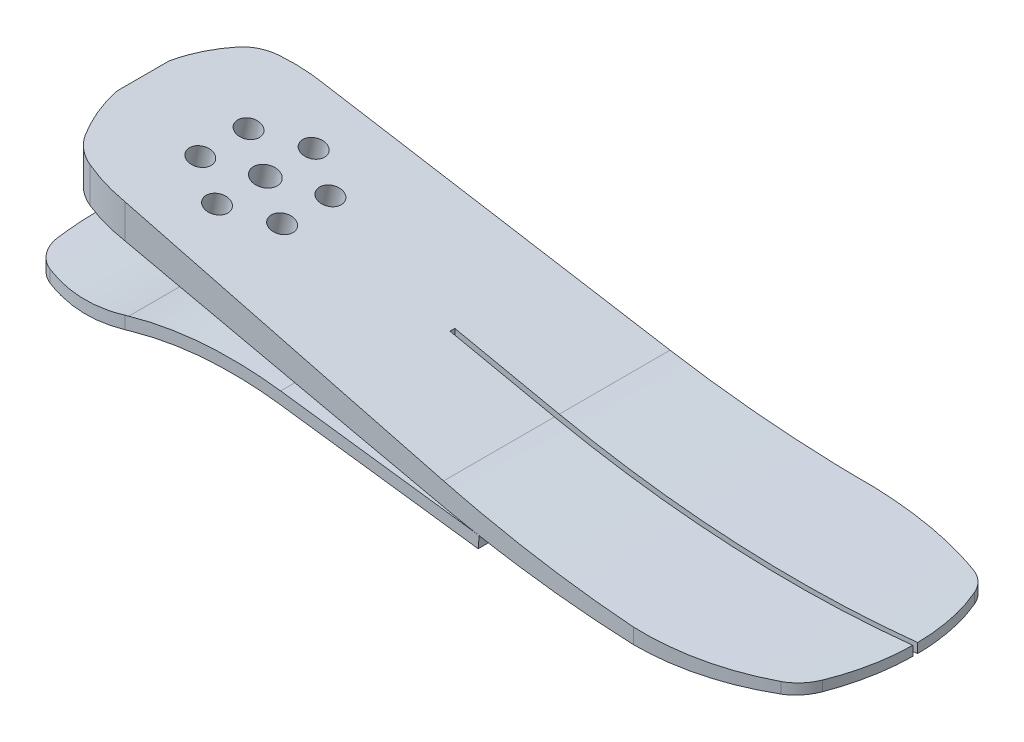
SolidWorks part; units mm, degrees
material "Thornel Mat VMA"
ref_plane "前视基准面" through (0, 0, 0) normal (0, 0, 1) x (1, 0, 0)
ref_plane "上视基准面" through (0, 0, 0) normal (0, 1, 0) x (1, 0, 0)
ref_plane "右视基准面" through (0, 0, 0) normal (1, 0, 0) x (0, 0, -1)
sketch "草图1" plane through (0, 0, 0) normal (0, 0, 1) x (1, 0, 0)
  line L0 (0, 0) -> (-103.4048, 18.2331)
  line L1 (0, 0) -> (100, 0) construction
  line L2 (0, 0) -> (-198.6945, 0) construction
  line L3 (1.5628, 8.8633) -> (-101.842, 27.0963) construction
  line L4 (0.3473, 1.9696) -> (-103.0575, 20.2027) construction
  line L5 (1.5628, 8.8633) -> (0.3473, 1.9696) construction
  line L6 (-101.842, 27.0963) -> (0.9551, 5.4164)
  line L7 (100, 0) -> (99.6527, 1.9696)
  line L8 (-101.842, 27.0963) -> (-103.4048, 18.2331)
  arc A0 (0, 0) -> (100, 0) centre (50, 283.5641) ccw
  arc A1 (1.5628, 8.8633) -> (98.4372, 8.8633) centre (50, 283.5641) ccw construction
  arc A2 (0.3473, 1.9696) -> (99.6527, 1.9696) centre (50, 283.5641) ccw construction
  arc A3 (0.9551, 5.4164) -> (99.0449, 5.4164) centre (50, 283.5641) ccw construction
  arc A4 (0.9551, 5.4164) -> (99.6527, 1.9696) centre (60.1694, 286.1865) ccw
  dimension "D6" = 5.5
  dimension "D1" = 10
  dimension "D2" = 105
  dimension "D3" = 100
  dimension "D4" = 9
  dimension "D5" = 2
extrude "凸台-拉伸1" add sketch "草图1" along normal blind 80 contours A4 L6 L8 L0 A0 L7 region at (-22.8734, 8.7177, 0)
sketch "草图2" plane through (0, 0, 0) normal (0, 1, 0) x (1, 0, 0)
  line L0 (-103.4048, -40) -> (90, -40) construction
  line L1 (-103.4048, -80) -> (-103.4048, 0) construction
  line L2 (-103.4048, -40) -> (-119.5906, -40) construction
  line L3 (-81.4048, -15) -> (-81.4048, -65) construction
  line L4 (50, -10) -> (50, -70) construction
  line L5 (0, 0) -> (0, -93.6691) construction
  line L6 (-81.4048, -15) -> (50, -10)
  line L7 (-81.4048, -65) -> (50, -70)
  arc A0 (10.1625, -11.5158) -> (10.1625, -68.4842) centre (45, -40) ccw construction
  arc A1 (80.5986, -16.083) -> (50, -10) centre (50, -90) ccw
  arc A2 (2.3095, -25.7691) -> (-26.6475, -67.0835) centre (50, -90) ccw construction
  arc A3 (85.852, -58.8709) -> (85.852, -21.1291) centre (45, -40) ccw
  arc A4 (80.5986, -16.083) -> (85.852, -21.1291) centre (76.7738, -25.3226) cw
  arc A5 (80.5986, -63.917) -> (85.852, -58.8709) centre (76.7738, -54.6774) ccw
  arc A6 (80.5986, -63.917) -> (50, -70) centre (50, 10) cw
  arc A7 (-97.2305, -20.9921) -> (-97.2305, -59.0079) centre (-64.9048, -40) ccw
  arc A8 (-59.2135, -77.0656) -> (-47.8638, -40) centre (-81.4048, -50) ccw construction
  arc A9 (-81.4048, -15) -> (-91.4925, -16.4853) centre (-81.4048, -50) ccw
  arc A10 (-59.2135, -77.0656) -> (-38.5047, -13.3676) centre (-64.9048, -40) ccw construction
  arc A11 (-81.4048, -65) -> (-91.4925, -63.5147) centre (-81.4048, -30) cw
  arc A12 (-91.4925, -63.5147) -> (-97.2305, -59.0079) centre (-88.6103, -53.9391) cw
  arc A13 (-97.2305, -20.9921) -> (-91.4925, -16.4853) centre (-88.6103, -26.0609) cw
  point P38 (-95.13, -62.1966)
  point P41 (-95.13, -17.8034)
  dimension "D7" = 90
  dimension "D8" = 160
  dimension "D9" = 10
  dimension "D10" = 5
  dimension "D11" = 70
  dimension "D12" = 75
  dimension "D4" = 10
  dimension "D1" = 50
  dimension "D2" = 60
  dimension "D5" = 50
  dimension "D6" = 22
  dimension "D13" = 16.5
extrude "切除-拉伸1" cut sketch "草图2" against normal blind 80 and the other way blind 80 flip side to cut
sketch "草图5" plane through (0, 0, 0) normal (0, 0, 1) x (1, 0, 0)
  line L0 (0, -2.1872) -> (-41.2678, 1.4302) construction
  line L1 (50, -4.3744) -> (-151.6273, -4.3744) construction
  line L2 (0, 0) -> (0, -4.3744) construction
  line L3 (50, -7.3744) -> (-151.6273, -7.3744) construction
  line L4 (-50, 45.5691) -> (-50, -83.0319) construction
  line L5 (-110, 54.322) -> (-110, -76.7901) construction
  line L6 (-50, 2.1956) -> (-111.6648, 7.6009) construction
  line L7 (0, -2.1872) -> (10, -3.0638) construction
  line L8 (10, 38.2491) -> (10, -59.0644) construction
  line L9 (0.131, -0.6929) -> (-41.1369, 2.9244)
  line L10 (0.131, -0.6929) -> (10.131, -1.5695)
  line L11 (-0.131, -3.6815) -> (-41.3988, -0.0641)
  line L12 (-0.131, -3.6815) -> (9.869, -4.5581)
  line L13 (9.869, -4.5581) -> (10.131, -1.5695)
  line L14 (-134.0122, -2.9192) -> (-134.7396, -5.8297)
  arc A0 (0, -2.1872) -> (50, -4.3744) centre (50, 568.2218) ccw construction
  arc A1 (-41.2678, 1.4302) -> (-79.9205, -2.769) centre (-50, -98.1878) ccw construction
  arc A2 (-64.5755, 3.4732) -> (-50, 12.4938) centre (-110, 93.1566) ccw construction
  arc A3 (-84.6272, -4.3744) -> (-15.3728, -4.3744) centre (-50, -98.1878) ccw construction
  arc A4 (-134.3759, -4.3744) -> (-79.9205, -2.769) centre (-110, 93.1566) ccw construction
  arc A5 (-134.0122, -2.9192) -> (-80.3694, -1.3377) centre (-110, 93.1566) ccw
  arc A6 (-41.1369, 2.9244) -> (-80.3694, -1.3377) centre (-50, -98.1878) ccw
  arc A7 (-134.7396, -5.8297) -> (-79.4717, -4.2003) centre (-110, 93.1566) ccw
  arc A8 (-41.3988, -0.0641) -> (-79.4717, -4.2003) centre (-50, -98.1878) ccw
  dimension "D3" = 60
  dimension "D4" = 200
  dimension "D1" = 3
  dimension "D2" = 50
  dimension "D5" = 60
  dimension "D6" = 1.5
  dimension "D7" = 1.5
extrude "凸台-拉伸2" add sketch "草图5" along normal blind 80
sketch "草图3" plane through (1.1344, 5.3786, 0) normal (0.2064, 0.9785, 0) x (0.9785, -0.2064, 0)
  line L0 (-0.1832, -40) -> (-123.6089, -40) construction
  line L1 (-0.1832, -68.1338) -> (-0.1832, -11.8662) construction
  circle A0 centre (-74.208, -40) radius 3
  circle A1 centre (-74.208, -28) radius 2.75
  circle A2 centre (-63.8157, -34) radius 2.75
  circle A3 centre (-63.8157, -46) radius 2.75
  circle A4 centre (-74.208, -52) radius 2.75
  circle A5 centre (-84.6003, -46) radius 2.75
  circle A6 centre (-84.6003, -34) radius 2.75
  circle A7 centre (-74.208, -40) radius 12 construction
  point P21 (-74.208, -40)
  dimension "D4" = 6
  dimension "D2" = 5.5
  dimension "D3" = 24
  dimension "D1" = 6
extrude "切除-拉伸2" cut sketch "草图3" against normal blind 9
sketch "草图4" plane through (0, 0, 0) normal (0, 1, 0) x (1, 0, 0)
  line L0 (124.5073, -40) -> (-127.7087, -40) construction
  line L2 (-25, -39.4) -> (105, -39.4)
  line L3 (-25, -39.4) -> (-25, -40.6)
  line L4 (-25, -40.6) -> (105, -40.6)
  line L5 (105, -39.4) -> (105, -40.6)
  arc A0 (85.852, -58.8709) -> (85.852, -21.1291) centre (45, -40) ccw construction
  dimension "D1" = 1.2
  dimension "D2" = 0.6
  dimension "D3" = 70
  dimension "D4" = 60
extrude "切除-拉伸3" cut sketch "草图4" against normal blind 8 and the other way blind 16
sketch "草图6" plane through (0, 0, 0) normal (0, 1, 0) x (1, 0, 0)
  line L0 (-81.4048, -15) -> (-81.4048, -65) construction
  line L1 (-81.4048, -40) -> (-155.8154, -40) construction
  line L2 (-111.4048, -40) -> (-111.4048, -90.6586) construction
  line L3 (136.1875, -6.7205) -> (136.1875, -73.2795)
  line L16 (0.9551, -68.1338) -> (0.9551, -40.6)
  line L17 (0.9551, -40.6) -> (-25, -40.6)
  line L18 (-25, -40.6) -> (-25, -39.4)
  line L19 (-25, -39.4) -> (0.9551, -39.4)
  line L20 (0.9551, -39.4) -> (0.9551, -11.8662)
  line L21 (0.9551, -11.8662) -> (-81.4048, -15)
  line L22 (-101.842, -33.5273) -> (-101.842, -46.4727)
  line L23 (-81.4048, -65) -> (0.9551, -68.1338)
  line L29 (136.1875, -6.7205) -> (-81.4048, -15)
  line L31 (-81.4048, -65) -> (136.1875, -73.2795)
  arc A0 (-110.6385, -27.6438) -> (-110.6385, -52.3562) centre (-11.4048, -40) ccw
  arc A1 (-130.1388, -40) -> (-21.9056, -67.264) centre (-81.4048, -75) ccw construction
  arc A2 (-81.4048, -15) -> (-104.5772, -19.6553) centre (-81.4048, -75) ccw
  arc A3 (-110.6385, -27.6438) -> (-104.5772, -19.6553) centre (-100.7151, -28.8794) cw
  arc A4 (-110.6385, -52.3562) -> (-104.5772, -60.3447) centre (-100.7151, -51.1206) ccw
  arc A5 (-81.4048, -65) -> (-104.5772, -60.3447) centre (-81.4048, -5) cw
  arc A12 (-81.4048, -15) -> (-91.4925, -16.4853) centre (-81.4048, -50) ccw
  arc A13 (-91.4925, -16.4853) -> (-97.2305, -20.9921) centre (-88.6103, -26.0609) ccw
  arc A14 (-97.2305, -20.9921) -> (-101.842, -33.5273) centre (-64.9048, -40) ccw
  arc A15 (-101.842, -46.4727) -> (-97.2305, -59.0079) centre (-64.9048, -40) ccw
  arc A16 (-97.2305, -59.0079) -> (-91.4925, -63.5147) centre (-88.6103, -53.9391) ccw
  arc A17 (-91.4925, -63.5147) -> (-81.4048, -65) centre (-81.4048, -30) ccw
  dimension "D2" = 30
  dimension "D3" = 200
  dimension "D4" = 120
  dimension "D5" = 10
  dimension "D1" = 0
extrude "切除-拉伸4" cut sketch "草图6" against normal blind 80 and the other way blind 80 flip side to cut
sketch "草图7" plane through (0, 0, 0) normal (0, 1, 0) x (1, 0, 0)
  line L1 (-25, -40.6) -> (-173.8533, -40.6)
  line L2 (-25, -40.6) -> (-25, -39.4)
  line L3 (-25, -39.4) -> (-173.8533, -39.4)
  line L4 (-173.8533, -40.6) -> (-173.8533, -39.4)
  dimension "D1" = 1.2
extrude "切除-拉伸5" cut sketch "草图7" against normal blind 10 and the other way blind 4
sketch "草图8" plane through (0, 0, 0) normal (0, 0, 1) x (1, 0, 0)
  line L0 (-110.6385, -8.8724) -> (65.321, -3.9665)
  line L1 (65.321, -3.9665) -> (69.681, -3.135)
  line L2 (69.681, -3.135) -> (69.681, -3.945)
  line L3 (69.681, -3.945) -> (-110.6385, -8.9724)
  line L4 (-110.6385, -8.9724) -> (-110.6385, -8.8724)
  arc A0 (50, -4.3744) -> (80.5986, -2.744) centre (50, 283.5641) ccw construction
  dimension "D1" = 0.1
extrude "凸台-拉伸3" add sketch "草图8" along normal blind 30 from offset 25
sketch "草图9" plane through (0.164, -5.8832, 0) normal (0.0279, -0.9996, 0) x (0.9996, 0.0279, 0)
  line L0 (89.9169, 70) -> (89.9169, 10)
  line L1 (-111.6068, 70) -> (-111.6068, 10)
  line L2 (89.9169, 70) -> (-111.6068, 70)
  line L3 (89.9169, 10) -> (-111.6068, 10)
